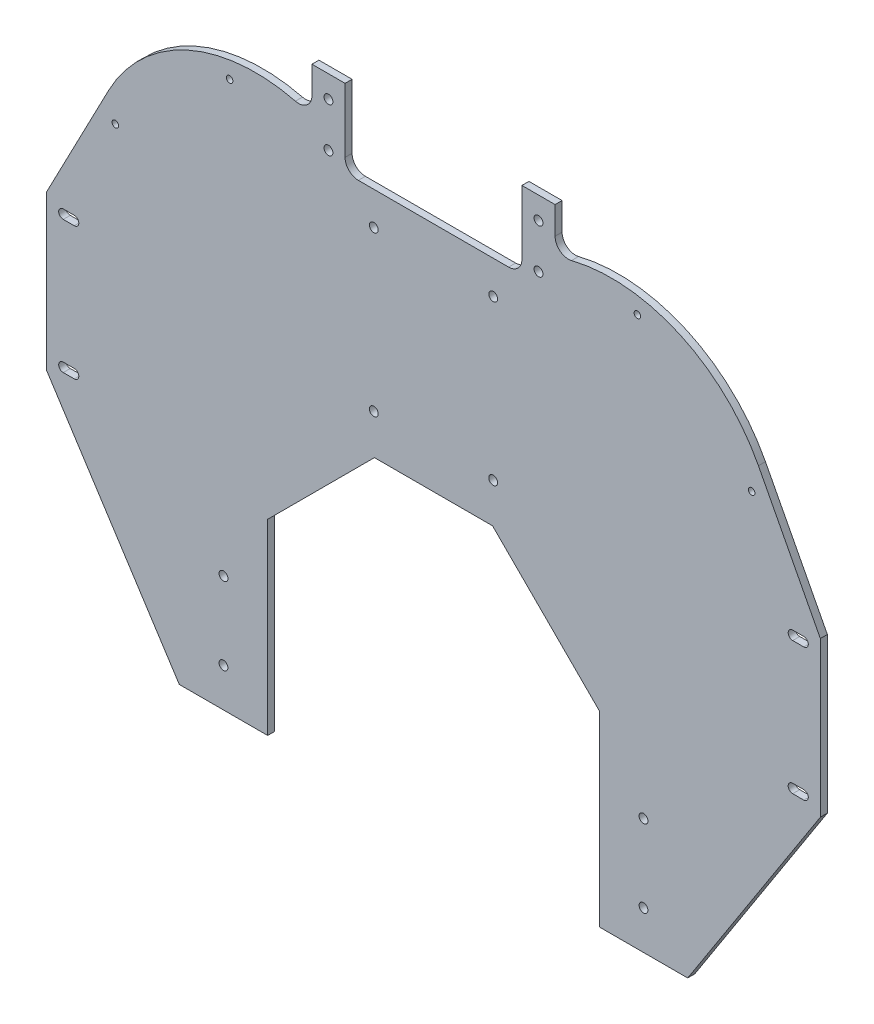
SolidWorks part; units mm, degrees
ref_plane "Front Plane" through (0, 0, 0) normal (0, 0, 1) x (1, 0, 0)
ref_plane "Top Plane" through (0, 0, 0) normal (0, 1, 0) x (1, 0, 0)
ref_plane "Right Plane" through (0, 0, 0) normal (1, 0, 0) x (0, 0, -1)
sketch "Sketch1" plane through (0, 0, 0) normal (0, 0, 1) x (1, 0, 0)
  line L1 (-100, -75) -> (100, -75)
  line L2 (-100, -75) -> (-100, 75)
  line L3 (-100, 75) -> (100, 75)
  line L4 (100, -75) -> (100, 75)
  line L5 (-100, -75) -> (100, 75) construction
  line L6 (-100, 75) -> (100, -75) construction
  line L8 (-47.5, 40) -> (47.5, 40) construction
  line L9 (0, 75) -> (0, -75) construction
  line L10 (-27, -52) -> (27, -52) construction
  line L11 (-27, -52) -> (-27, 20) construction
  line L12 (-27, 20) -> (27, 20) construction
  line L13 (27, -52) -> (27, 20) construction
  line L14 (-27, -52) -> (27, 20) construction
  line L15 (-27, 20) -> (27, -52) construction
  line L23 (-55, 70) -> (55, 70)
  line L24 (-55, 70) -> (-55, -70)
  line L25 (-55, -70) -> (55, -70)
  line L26 (55, 70) -> (55, -70)
  line L27 (-55, 70) -> (55, -70) construction
  line L28 (-55, -70) -> (55, 70) construction
  line L29 (-40, 70) -> (40, 70)
  line L30 (-40, 70) -> (-40, 35)
  line L31 (-40, 35) -> (40, 35)
  line L32 (40, 70) -> (40, 35)
  line L33 (-40, 70) -> (40, 35) construction
  line L34 (-40, 35) -> (40, 70) construction
  circle A2 centre (-47.5, 40) radius 2
  circle A3 centre (47.5, 40) radius 2
  circle A4 centre (-27, 20) radius 2
  circle A5 centre (27, 20) radius 2
  circle A6 centre (27, -52) radius 2
  circle A7 centre (-27, -52) radius 2
  circle A8 centre (-47.5, 60) radius 2
  circle A9 centre (47.5, 60) radius 2
  point P0 (0, 0)
  point P15 (0, 40)
  point P18 (0, -16)
  point P56 (0, 0)
  point P63 (0, 52.5)
  dimension "D3" = 4
  dimension "D4" = 20
  dimension "D5" = 4
  dimension "D8" = 4
  dimension "D1" = 150
  dimension "D2" = 200
  dimension "D6" = 72
  dimension "D7" = 54
  dimension "D14" = 30
  dimension "D15" = 140
  dimension "D16" = 110
  dimension "D17" = 95
  dimension "D18" = 20
  dimension "D19" = 35
  dimension "D20" = 80
extrude "Boss-Extrude1" add sketch "Sketch1" along normal blind 3.175 contours L23 L32 L31 L30 L24 L25 L26 A7 A6 A5 A4 A3 A2 region at (0, -11.8972, 0)
sketch "Sketch2" plane through (0, 0, 0) normal (0, 0, 1) x (1, 0, 0)
  line L0 (-55, -70) -> (-100.8579, -115.8579) construction
  line L1 (-55, 70) -> (-55, -70) construction
  line L2 (-55, -41.7157) -> (-115, -101.7157)
  line L3 (-26.7157, -70) -> (-86.7157, -130)
  line L4 (-55, -70) -> (55, -70) construction
  line L5 (-115, -101.7157) -> (-86.7157, -130)
  line L6 (-115, -101.7157) -> (-115, -203)
  line L7 (-75, -118.2843) -> (-75, -203)
  line L8 (-75, -203) -> (-115, -203)
  line L9 (0, 75) -> (0, -75) construction
  line L10 (-55, -41.7157) -> (-26.7157, -70)
  line L11 (-55, 70) -> (-55, -70) construction
  line L12 (-75, -203) -> (-115, -203) construction
  line L13 (-55, -70) -> (55, -70) construction
  line L14 (-55, 70) -> (-55, -70) construction
  circle A0 centre (-95, -150.5) radius 2
  circle A1 centre (-95, -185.5) radius 2
  dimension "D5" = 4
  dimension "D6" = 4
  dimension "D1" = 135
  dimension "D2" = 40
  dimension "D3" = 40
  dimension "D4" = 75
extrude "Boss-Extrude2" add sketch "Sketch2" along normal blind 3.175 contours L8 L7 L3 L5 L6 | L10 L2 L5 L3 region at (-70.8579, -85.8579, 0) region at (-95.9289, -160.2024, 0)
mirror "Mirror1" about plane through (0, 0, 0) normal (1, 0, 0) of "Boss-Extrude2"
sketch "Sketch3" plane through (0, 0, 3.175) normal (0, 0, 1) x (1, 0, 0)
  line L0 (0, 0) -> (0, 95.843) construction
  line L1 (-80.5, -21) -> (-92.2213, 45.4745) construction
  line L2 (-80.5, -21) -> (-143.9293, 2.0864) construction
  line L3 (-80.5, -21) -> (-148, -21) construction
  line L4 (-42.1979, -85.4821) -> (-26.7157, -70)
  line L5 (-26.7157, -70) -> (-23.7197, -70)
  line L6 (-26.7157, -70) -> (26.7157, -70) construction
  line L7 (-26.7157, -70) -> (-75, -118.2843) construction
  line L8 (26.7157, -70) -> (23.7197, -70)
  line L9 (42.1979, -85.4821) -> (26.7157, -70)
  circle A0 centre (-80.5, -21) radius 60 construction
  circle A1 centre (-80.5, -21) radius 75
  circle A2 centre (-80.5, -21) radius 67.5 construction
  circle A3 centre (-92.2213, 45.4745) radius 1.4732
  circle A4 centre (-143.9293, 2.0864) radius 1.4732
  circle A5 centre (-47.5, 40) radius 2 construction
  circle A6 centre (143.9293, 2.0864) radius 1.4732
  circle A7 centre (92.2213, 45.4745) radius 1.4732
  circle A8 centre (80.5, -21) radius 75
  circle A9 centre (-47.5, 40) radius 2
  circle A10 centre (-27, 20) radius 2
  circle A11 centre (-27, -52) radius 2
  circle A12 centre (-27, 20) radius 2 construction
  circle A13 centre (-27, -52) radius 2 construction
  circle A14 centre (47.5, 40) radius 2
  circle A15 centre (27, 20) radius 2
  circle A16 centre (27, -52) radius 2
  line M5 (-26.7157, -70) -> (26.7157, -70)
  line M6 (26.7157, -70) -> (75, -118.2843)
  line M10 (115, -101.7157) -> (55, -41.7157)
  line M11 (55, -41.7157) -> (55, 70)
  line M13 (40, 70) -> (40, 35)
  line M14 (40, 35) -> (-40, 35)
  line M15 (-40, 35) -> (-40, 70)
  line M17 (-55, 70) -> (-55, -41.7157)
  line M18 (-55, -41.7157) -> (-115, -101.7157)
  line M22 (-75, -118.2843) -> (-26.7157, -70)
  circle M23 centre (-47.5, 40) radius 2
  circle M24 centre (47.5, 40) radius 2
  circle M25 centre (-27, 20) radius 2
  circle M26 centre (27, 20) radius 2
  circle M27 centre (27, -52) radius 2
  circle M28 centre (-27, -52) radius 2
  dimension "D1" = 120
  dimension "D3" = 7.5
  dimension "D4" = 61
  dimension "D8" = 2.9464
  dimension "D5" = 80
  dimension "D6" = 20
  dimension "D7" = 161
  dimension "D2" = 15
extrude "Boss-Extrude3" add sketch "Sketch3" against normal up to surface (3.175 mm away) contours A1 A4 A3 M17 M18 | A1 M15 M17 M18 M22 M5 M14 M28 M25 M23 | A8 M10 M11 M13 M14 M5 M6 M27 M26 M24 | A8 A6 A7 M11 M10 region at (-42.8459, -33.3688, 3.175) region at (-102.3675, -14.0811, 3.175) region at (42.8459, -33.3688, 3.175) region at (102.3675, -14.0811, 3.175) up to face at (0, -62.524, 0)
sketch "Sketch4" plane through (0, 0, 3.175) normal (0, 0, 1) x (1, 0, 0)
  line L0 (-175, -110) -> (-115, -203)
  line L1 (-100, -110) -> (-115, -110) construction
  line L2 (-100, -110) -> (-100, -40)
  line L3 (-100, -40) -> (-152.4428, -40)
  line L4 (-175, -110) -> (-175, -40)
  line L5 (-100, -110) -> (-175, -40) construction
  line L6 (-100, -40) -> (-175, -110) construction
  line L8 (-115, -101.7157) -> (-115, -203) construction
  line L9 (-115, -110) -> (-115, -203)
  line L10 (-151.1989, -110) -> (-175, -110) construction
  line L11 (-175, -40) -> (-146.9976, 13.6853)
  line L12 (-152.4428, -40) -> (-152.8464, -40.7738)
  line L13 (-152.4428, -40) -> (-175, -40) construction
  line L14 (-175, -75) -> (-100, -75) construction
  line L15 (-165, -40) -> (-165, -75) construction
  line L18 (-100, -110) -> (-100, -101.7157)
  line L19 (-100, -101.7157) -> (-115, -101.7157)
  line L20 (-115, -110) -> (-115, -101.7157)
  line L21 (-100, -110) -> (-115, -101.7157) construction
  line L22 (-100, -101.7157) -> (-115, -110) construction
  line L23 (-162.5, -45) -> (-167.5, -45) construction
  line L24 (-162.5, -47.05) -> (-167.5, -47.05)
  line L25 (-162.5, -42.95) -> (-167.5, -42.95)
  line L26 (-162.5, -105) -> (-167.5, -105) construction
  line L27 (-162.5, -102.95) -> (-167.5, -102.95)
  line L28 (-162.5, -107.05) -> (-167.5, -107.05)
  circle A0 centre (-143.9293, 2.0864) radius 1.4732
  circle A1 centre (-143.9293, 2.0864) radius 1.4732 construction
  arc A2 (-55, 49.5319) -> (-105.1261, -91.8418) centre (-80.5, -21) ccw construction
  arc A3 (-152.8464, -40.7738) -> (-146.9976, 13.6853) centre (-80.5, -21) cw
  circle A4 centre (-165, -45) radius 2.05 construction
  circle A6 centre (-165, -105) radius 2.05 construction
  arc A7 (-162.5, -47.05) -> (-162.5, -42.95) centre (-162.5, -45) ccw
  arc A8 (-167.5, -42.95) -> (-167.5, -47.05) centre (-167.5, -45) ccw
  arc A9 (-162.5, -102.95) -> (-162.5, -107.05) centre (-162.5, -105) cw
  arc A10 (-167.5, -107.05) -> (-167.5, -102.95) centre (-167.5, -105) cw
  point P0 (-137.5, -75)
  point P36 (-107.5, -105.8579)
  point P38 (-165, -45)
  point P48 (-165, -105)
  arc M14 (-55, 49.5319) -> (-105.1261, -91.8418) centre (-80.5, -21) ccw
  line M15 (-105.1261, -91.8418) -> (-115, -101.7157)
  line M16 (-115, -101.7157) -> (-115, -203)
  dimension "D7" = 4.1
  dimension "D9" = 2.05
  dimension "D1" = 100
  dimension "D2" = 40
  dimension "D3" = 75
  dimension "D4" = 70
  dimension "D6" = 20
  dimension "D8" = 10
  dimension "D10" = 5
  dimension "D11" = 5
extrude "Boss-Extrude4" add sketch "Sketch4" against normal up to surface (3.175 mm away) contours L11 L4 L0 A8 L25 A7 L24 L28 A10 L27 A9 M16 M15 M14 region at (-143.8938, -104.7844, 3.175) up to face at (0, -53.8091, 0)
mirror "Mirror2" about plane through (0, 0, 0) normal (1, 0, 0) of "Boss-Extrude4"
fillet "Fillet1" radius 6 4 edges at (-55, 49.5319, 1.5875) (-40, 35, 1.5875) (40, 35, 1.5875) (55, 49.5319, 1.5875)
